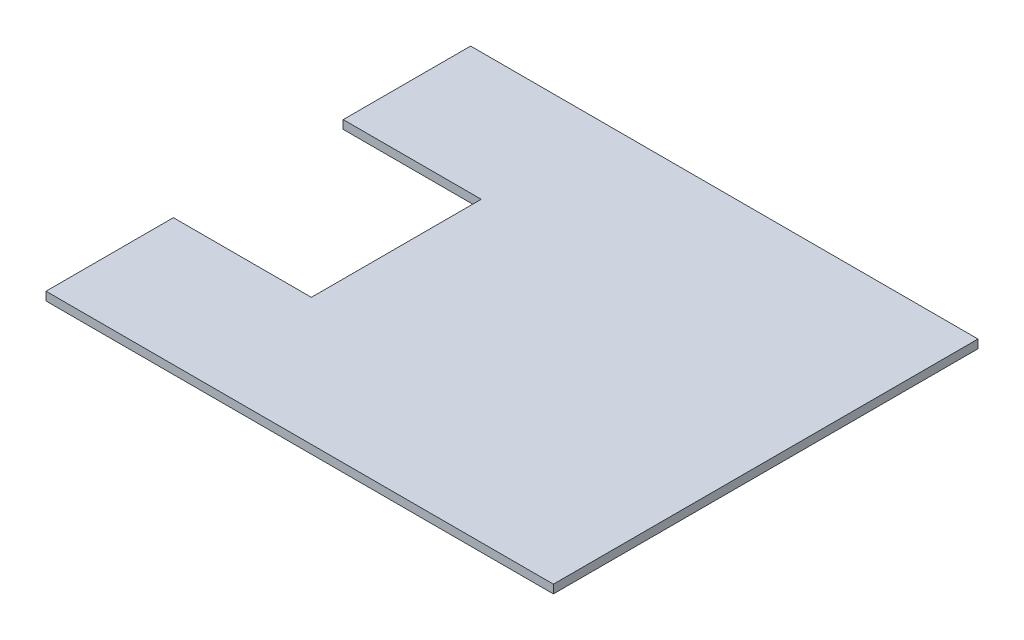
SolidWorks part; units mm, degrees
ref_plane "Alzado" through (0, 0, 0) normal (0, 0, 1) x (1, 0, 0)
ref_plane "Planta" through (0, 0, 0) normal (0, 1, 0) x (1, 0, 0)
ref_plane "Vista lateral" through (0, 0, 0) normal (1, 0, 0) x (0, 0, -1)
sketch "Croquis1" plane through (0, 0, 0) normal (0, 1, 0) x (1, 0, 0)
  line L0 (208.1762, 0) -> (-235.2506, 0) construction
  line L1 (119.5, -100) -> (-119.5, -100)
  line L2 (119.5, -100) -> (119.5, 100)
  line L3 (119.5, 100) -> (-119.5, 100)
  line L4 (-119.5, -100) -> (-119.5, 100) construction
  line L5 (119.5, -100) -> (-119.5, 100) construction
  line L6 (119.5, 100) -> (-119.5, -100) construction
  line L7 (-119.5, 40) -> (-54.5, 40)
  line L8 (-54.5, 40) -> (-54.5, -40)
  line L9 (-119.5, 100) -> (-119.5, 40)
  line L10 (-119.5, -100) -> (-119.5, -40)
  line L11 (-119.5, -40) -> (-54.5, -40)
  point P0 (0, 0)
  point P12 (-54.5, 0)
  dimension "D1" = 239
  dimension "D2" = 200
  dimension "D3" = 65
  dimension "D4" = 40
extrude "Saliente-Extruir1" add sketch "Croquis1" along normal blind 4
